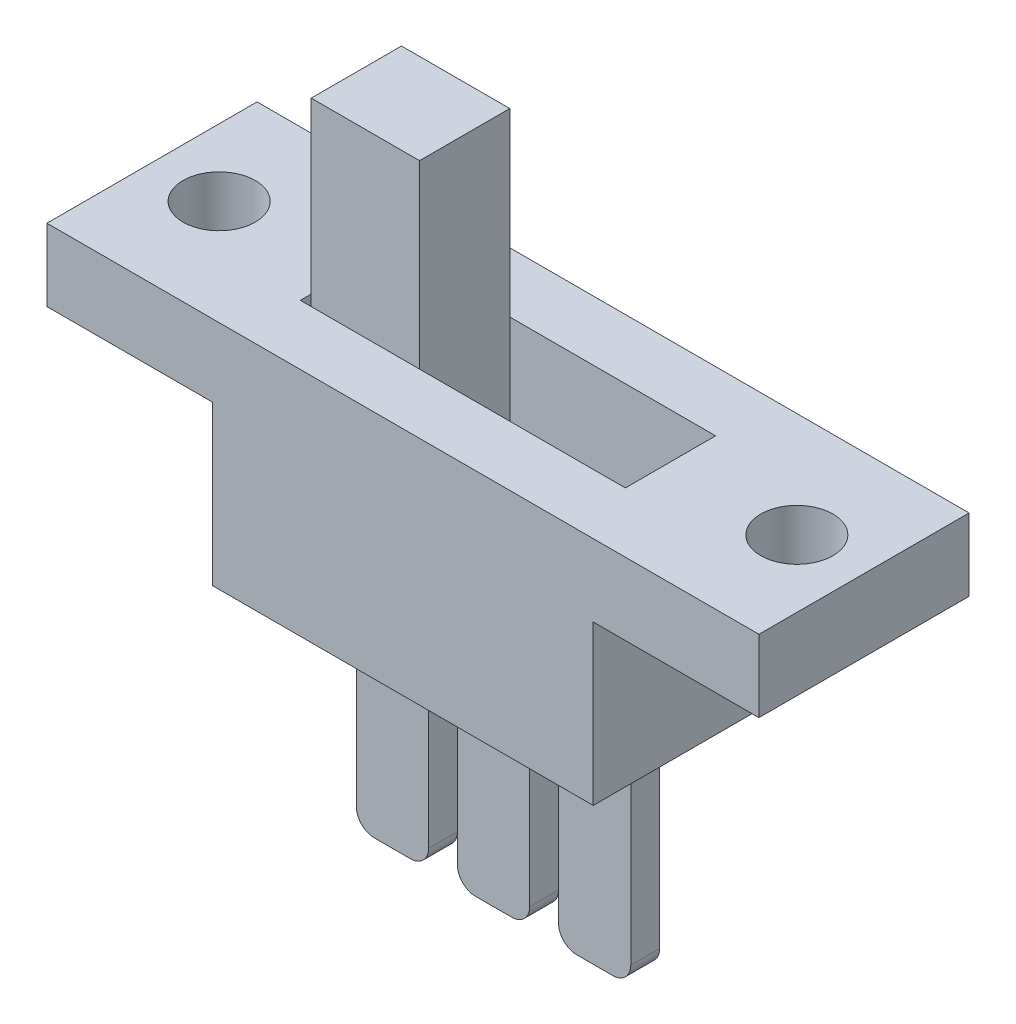
SolidWorks part; units mm, degrees
ref_plane "Front Plane" through (0, 0, 0) normal (0, 0, 1) x (1, 0, 0)
ref_plane "Top Plane" through (0, 0, 0) normal (0, 1, 0) x (1, 0, 0)
ref_plane "Right Plane" through (0, 0, 0) normal (1, 0, 0) x (0, 0, -1)
sketch "Sketch1" plane through (0, 0, 0) normal (0, 1, 0) x (1, 0, 0)
  line L0 (-8, 0) -> (8, 0) construction
  line L1 (-9.86, 2.91) -> (9.86, 2.91)
  line L2 (-9.86, 2.91) -> (-9.86, -2.91)
  line L3 (-9.86, -2.91) -> (9.86, -2.91)
  line L4 (9.86, 2.91) -> (9.86, -2.91)
  line L5 (-9.86, 2.91) -> (9.86, -2.91) construction
  line L6 (-9.86, -2.91) -> (9.86, 2.91) construction
  line L8 (-4.5, 1.25) -> (4.5, 1.25)
  line L9 (-4.5, 1.25) -> (-4.5, -1.25)
  line L10 (-4.5, -1.25) -> (4.5, -1.25)
  line L11 (4.5, 1.25) -> (4.5, -1.25)
  line L12 (-4.5, 1.25) -> (4.5, -1.25) construction
  line L13 (-4.5, -1.25) -> (4.5, 1.25) construction
  line L14 (-4.2, 1.25) -> (-1.2, 1.25)
  line L15 (-4.2, 1.25) -> (-4.2, -1.25)
  line L16 (-4.2, -1.25) -> (-1.2, -1.25)
  line L17 (-1.2, 1.25) -> (-1.2, -1.25)
  line L18 (-5.27, 2.91) -> (5.27, 2.91)
  line L19 (-5.27, 2.91) -> (-5.27, -2.91)
  line L20 (-5.27, -2.91) -> (5.27, -2.91)
  line L21 (5.27, 2.91) -> (5.27, -2.91)
  line L22 (-5.27, 2.91) -> (5.27, -2.91) construction
  line L23 (-5.27, -2.91) -> (5.27, 2.91) construction
  circle A0 centre (8, 0) radius 1
  circle A1 centre (-8, 0) radius 1
  point P0 (0, 0)
  point P10 (0, 0)
  point P11 (0, 0)
  point P20 (0, 0)
  dimension "D1" = 2
  dimension "D2" = 2
  dimension "D3" = 19.72
  dimension "D4" = 16
  dimension "D5" = 5.82
  dimension "D6" = 2.5
  dimension "D7" = 9
  dimension "D8" = 3
  dimension "D9" = 0.3
  dimension "D10" = 10.54
extrude "Boss-Extrude1" add sketch "Sketch1" along normal blind 2 contours A1 | A0 | L3 L4 L1 L2 region at (8, 0, 0) region at (-8, 0, 0)
extrude "Boss-Extrude2" add sketch "Sketch1<3>" against normal blind 4.4 contours L21 L1 L19 L3 L8 L11 L10 L9 | L10 L11 L8 L9 region at (0, 0, -2.7896)
sketch "Sketch1<3>" plane through (0, 0, 0) normal (0, 1, 0) x (1, 0, 0) same geometry as "Sketch1"
extrude "Cut-Extrude1" cut sketch "Sketch1<4>" against normal blind 3 and the other way through all contours L8 L11 L10 L9
sketch "Sketch1<4>" plane through (0, 0, 0) normal (0, 1, 0) x (1, 0, 0) same geometry as "Sketch1"
extrude "Boss-Extrude3" add sketch "Sketch1<5>" along normal up to surface (2 mm away) from surface contours L17 L16 L15 L14 up to face at (-8, 2, 1) starting at face at (0, -3, 0)
sketch "Sketch1<5>" plane through (0, 0, 0) normal (0, 1, 0) x (1, 0, 0) same geometry as "Sketch1"
extrude "Boss-Extrude4" add sketch "Sketch1<6>" along normal blind 5 from surface contours L17 L16 L15 L14 starting at face at (1.65, 2, 0)
sketch "Sketch1<6>" plane through (0, 0, 0) normal (0, 1, 0) x (1, 0, 0) same geometry as "Sketch1"
sketch "Sketch2" plane through (0, 0, 0) normal (0, 1, 0) x (1, 0, 0)
  line L0 (-1.8, 0.4) -> (-1.8, -0.4)
  line L1 (-3.8, 0.4) -> (3.8, 0.4)
  line L2 (-3.8, 0.4) -> (-3.8, -0.4)
  line L3 (-3.8, -0.4) -> (3.8, -0.4)
  line L4 (3.8, 0.4) -> (3.8, -0.4)
  line L5 (-3.8, 0.4) -> (3.8, -0.4) construction
  line L6 (-3.8, -0.4) -> (3.8, 0.4) construction
  line L7 (-1, 0.4) -> (-1, -0.4)
  line L8 (1.8, 0.4) -> (1.8, -0.4)
  line L9 (1, 0.4) -> (1, -0.4)
  point P0 (0, 0)
  point P14 (3.8, 0)
  point P15 (-1, 0)
  dimension "D1" = 0.8
  dimension "D2" = 7.6
  dimension "D3" = 2
  dimension "D4" = 2
  dimension "D5" = 2
  dimension "D6" = 0.8
extrude "Boss-Extrude5" add sketch "Sketch2" against normal blind 6.32 from surface contours L2 L3 L0 L1 | L9 L1 L7 L3 | L1 L8 L3 L4 region at (-2.8, 0, 0) region at (0, 0, 0) region at (2.8, 0, 0) starting at face at (0, -4.4, 0)
fillet "Fillet1" radius 0.5 6 edges at (-3.8, -10.72, 0) (-1.8, -10.72, 0) (-1, -10.72, 0) (1, -10.72, 0) (1.8, -10.72, 0) (3.8, -10.72, 0)
